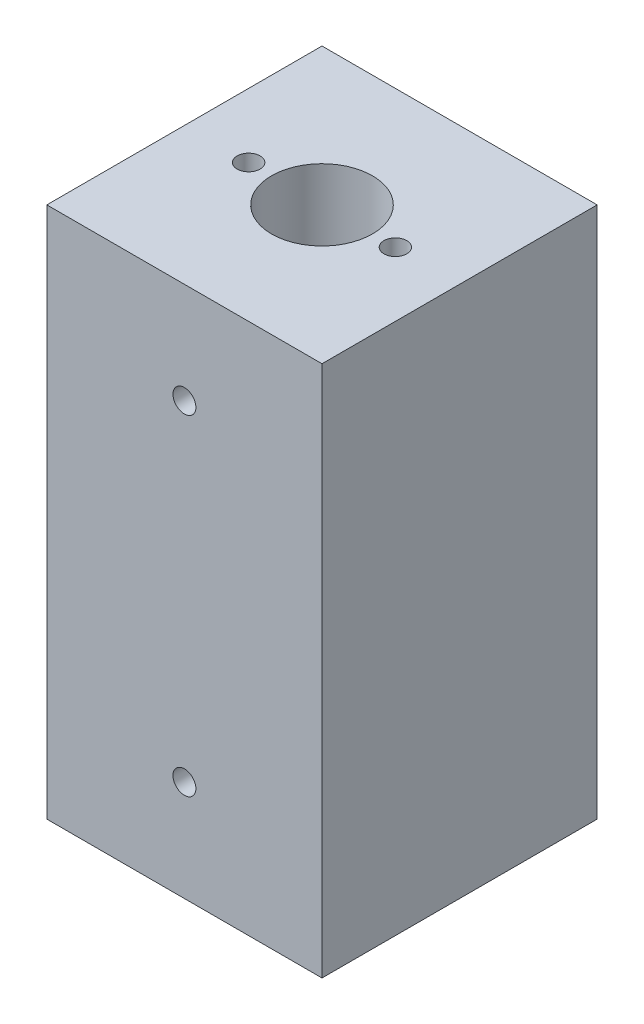
SolidWorks part; units mm, degrees
ref_plane "Front Plane" through (0, 0, 0) normal (0, 0, 1) x (1, 0, 0)
ref_plane "Top Plane" through (0, 0, 0) normal (0, 1, 0) x (1, 0, 0)
ref_plane "Right Plane" through (0, 0, 0) normal (1, 0, 0) x (0, 0, -1)
sketch "Sketch1" plane through (0, 0, 0) normal (0, 1, 0) x (1, 0, 0)
  line L0 (-40.8567, 0) -> (48.8389, 0) construction
  line L1 (0, 25.9431) -> (0, -21.8825) construction
  line L3 (-15, 15) -> (15, 15)
  line L4 (-15, 15) -> (-15, -15)
  line L5 (-15, -15) -> (15, -15)
  line L6 (15, 15) -> (15, -15)
  line L7 (-15, 15) -> (15, -15) construction
  line L8 (-15, -15) -> (15, 15) construction
  point P5 (0, 0)
  dimension "D1" = 30
  dimension "D2" = 30
extrude "Boss-Extrude1" add sketch "Sketch1" along normal blind 58
sketch "Sketch2" plane through (0, 58, 0) normal (0, 1, 0) x (1, 0, 0)
  circle A0 centre (0, 0) radius 5.5
  circle A1 centre (8, 0) radius 1.25
  circle A2 centre (-8, 0) radius 1.25
  point P7 (0, 0)
  dimension "D1" = 11
  dimension "D2" = 2.5
  dimension "D3" = 16
  dimension "D4" = 8
  dimension "D5" = 8
extrude "Cut-Extrude1" cut sketch "Sketch2" against normal blind 10
sketch "Sketch3" plane through (0, 48, 0) normal (0, 1, 0) x (1, 0, 0)
  circle A0 centre (0, 0) radius 5.5
  dimension "D1" = 11
extrude "Cut-Extrude2" cut sketch "Sketch3" against normal through all
sketch "Sketch4" plane through (0, 0, 15) normal (0, 0, 1) x (1, 0, 0)
  line L0 (-15, 58) -> (15, 58) construction
  line L1 (15, 58) -> (15, 0) construction
  line L2 (-15, 0) -> (15, 0) construction
  circle A0 centre (0, 47) radius 1.25
  circle A2 centre (0, 11) radius 1.25
  point P6 (0, 0)
  dimension "D1" = 36
  dimension "D2" = 2.5
  dimension "D3" = 11
  dimension "D4" = 15
  dimension "D5" = 11
extrude "Cut-Extrude3" cut sketch "Sketch4" against normal blind 8
mirror "Mirror1" about plane through (0, 0, 0) normal (0, 0, 1) of "Cut-Extrude3"
